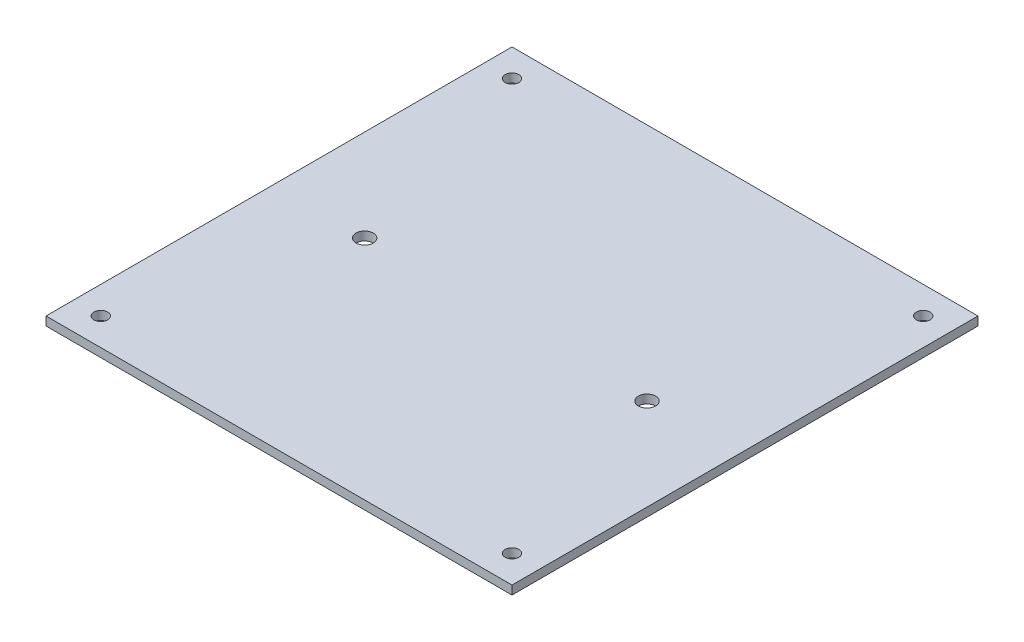
SolidWorks part; units mm, degrees
ref_plane "Front Plane" through (0, 0, 0) normal (0, 0, 1) x (1, 0, 0)
ref_plane "Top Plane" through (0, 0, 0) normal (0, 1, 0) x (1, 0, 0)
ref_plane "Right Plane" through (0, 0, 0) normal (1, 0, 0) x (0, 0, -1)
sketch "Sketch1" plane through (0, 0, 0) normal (0, 1, 0) x (1, 0, 0)
  line L0 (-93.5, 0) -> (93.5, 0) construction
  line L1 (-85, -85) -> (85, -85)
  line L2 (-85, -85) -> (-85, 85)
  line L3 (-85, 85) -> (85, 85)
  line L4 (85, -85) -> (85, 85)
  line L5 (-85, -85) -> (85, 85) construction
  line L6 (-85, 85) -> (85, -85) construction
  line L7 (-58.5, -61.25) -> (58.5, -61.25)
  line L8 (-58.5, -61.25) -> (-58.5, 61.25)
  line L9 (-58.5, 61.25) -> (58.5, 61.25)
  line L10 (58.5, -61.25) -> (58.5, 61.25)
  line L11 (-58.5, -61.25) -> (58.5, 61.25) construction
  line L12 (-58.5, 61.25) -> (58.5, -61.25) construction
  line L14 (0, -93.5) -> (0, 93.5) construction
  circle A0 centre (-51.5, -2.25) radius 3.15
  circle A1 centre (51.5, -2.25) radius 3.15
  circle A2 centre (-75, 75) radius 2.5
  circle A3 centre (75, 75) radius 2.5
  circle A4 centre (75, -75) radius 2.5
  circle A5 centre (-75, -75) radius 2.5
  point P0 (0, 0)
  point P6 (0, 0)
  dimension "D7" = 6.3
  dimension "D8" = 6.3
  dimension "D10" = 5
  dimension "D11" = 5
  dimension "D1" = 117
  dimension "D2" = 122.5
  dimension "D3" = 170
  dimension "D4" = 170
  dimension "D5" = 103
  dimension "D6" = 63.5
  dimension "D9" = 51.5
  dimension "D12" = 10
  dimension "D13" = 10
extrude "Boss-Extrude1" add sketch "Sketch1" along normal blind 3.175 contours L7 L10 L9 L8 A1 A0 | L1 L4 L3 L2 A4 A3 A2 L10 L7 L8 L9 A5 region at (-82.5958, 0, 0) region at (0, 0, -0.0098)
